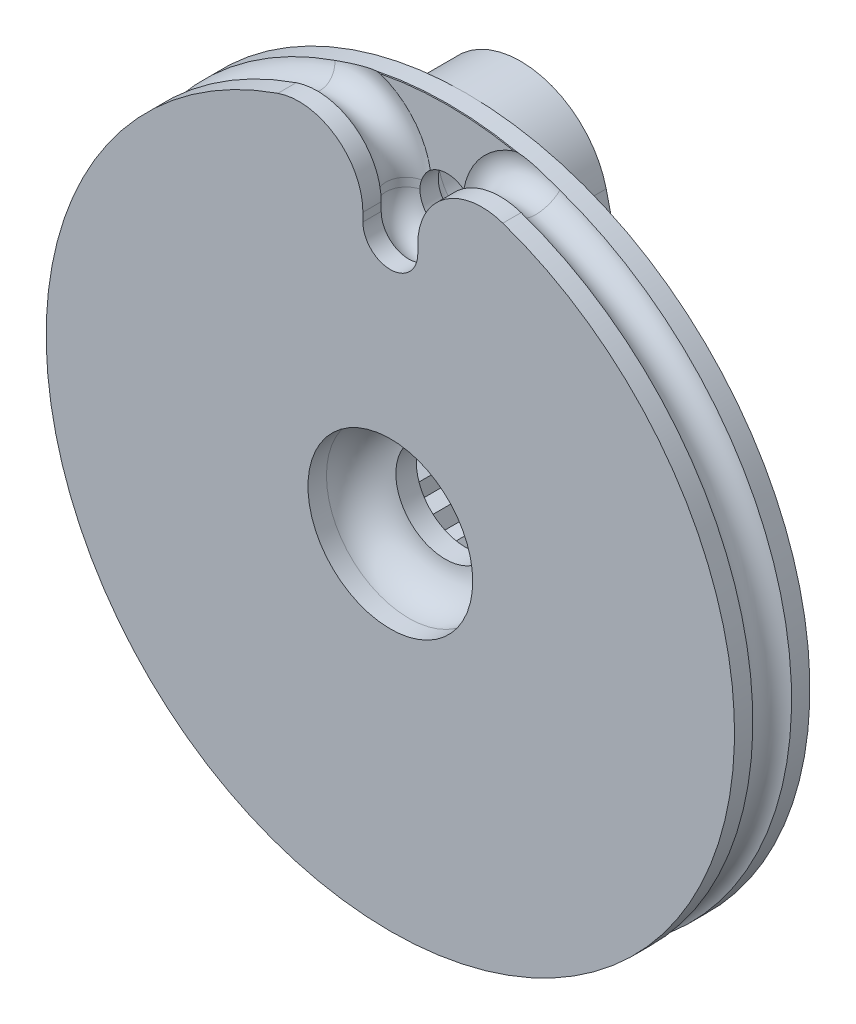
SolidWorks part; units mm, degrees
ref_plane "Front Plane" through (0, 0, 0) normal (0, 0, 1) x (1, 0, 0)
ref_plane "Top Plane" through (0, 0, 0) normal (0, 1, 0) x (1, 0, 0)
ref_plane "Right Plane" through (0, 0, 0) normal (1, 0, 0) x (0, 0, -1)
sketch "Sketch1" plane through (0, 0, 0) normal (0, 1, 0) x (1, 0, 0)
  line L0 (0, 0) -> (0, -4.9195) construction
  line L1 (-4, 1.0292) -> (-9.4, 1.0292)
  line L2 (0, 2.5292) -> (0, -1.0292)
  line L3 (0, -1.0292) -> (-9.4, -1.0292)
  line L5 (-9.4, 1.0292) -> (-9.4, 0.5292)
  line L6 (-9.4, -0.5292) -> (-9.4, -1.0292)
  line L7 (-9, 0.5907) -> (-9, -0.4988) construction
  line L10 (-4, 1.0292) -> (-4, 2.5292)
  line L11 (-4, 2.5292) -> (0, 2.5292)
  arc A0 (-9.4, -0.5292) -> (-9.4, 0.5292) centre (-9.55, 0) ccw
  point P2 (-3.8205, -1.0292)
  point P12 (0, 2.6484)
  point P15 (0, -1.0292)
  point P18 (0, -0.9285)
  point P19 (0, 0)
  point P20 (0, -1.0873)
  dimension "D4" = 0.55
  dimension "D1" = 18
  dimension "D2" = 0.5
  dimension "D3" = 0.5
  dimension "D5" = 0.15
  dimension "D6" = 1.5
  dimension "D7" = 8
revolve "Revolve1" add sketch "Sketch1" angle 360 about L0
sketch "Sketch2" plane through (0, 0, 1.0292) normal (0, 0, -1) x (-1, 0, 0)
  circle A2 centre (0, 0) radius 1.35
  circle A3 centre (0, 7) radius 0.75
  point P0 (0, 0)
  point P9 (0, 0)
  dimension "D3" = 2.7
  dimension "D4" = 1.5
  dimension "D5" = 7
extrude "Cut-Extrude1" cut sketch "Sketch2" along normal up to next
sketch "Sketch3" plane through (0, 0, 1.0292) normal (0, 0, 1) x (1, 0, 0)
  line L0 (0.75, 7) -> (0.75, 7.23)
  line L1 (-0.75, 7) -> (-0.75, 7.23)
  circle A2 centre (0, 7) radius 0.75 construction
  arc A3 (0.75, 7.23) -> (3.0719, 8.8839) centre (2.5, 7.23) cw
  circle A4 centre (0, 0) radius 9.4 construction
  arc A5 (3.0719, 8.8839) -> (-3.0719, 8.8839) centre (0, 0) ccw
  arc A6 (-0.75, 7) -> (0.75, 7) centre (0, 7) ccw
  arc A7 (-0.75, 7.23) -> (-3.0719, 8.8839) centre (-2.5, 7.23) ccw
  point P14 (0, 0)
  point P15 (1.5403, 9.2223)
  dimension "D2" = 1.75
extrude "Cut-Extrude2" cut sketch "Sketch3" against normal blind 0.8
sketch "Sketch5" plane through (0, 0, 1.0292) normal (0, 0, 1) x (1, 0, 0)
  circle A0 centre (0, 0) radius 2.25
  dimension "D1" = 4.5
extrude "Cut-Extrude4" cut sketch "Sketch5" against normal blind 1.5
fillet "Fillet2" radius 1 1 edges at (2.25, 0, -0.4708)
other "Move Face1" flip direction yes face at (0, 7.9097, 0.2292) offset 0.75 parameters "D1"=0.75
sketch "Sketch6" plane through (0, 0, 0) normal (0, 0, 1) x (1, 0, 0)
  line L0 (0.75, 7) -> (0.75, 7.23) construction
  line L1 (0.75, 7) -> (0.75, 7.23)
  line L2 (-0.75, 7.23) -> (-0.75, 7) construction
  line L3 (-0.75, 7.23) -> (-0.75, 7)
  arc A0 (2.7428, 8.963) -> (0.75, 7.23) centre (2.5, 7.23) ccw construction
  arc A1 (3.0719, 8.8839) -> (0.75, 7.23) centre (2.5, 7.23) ccw
  arc A3 (-0.75, 7) -> (0.75, 7) centre (0, 7) ccw
  arc A4 (-0.75, 7) -> (0.75, 7) centre (0, 7) ccw
  arc A6 (-0.75, 7.23) -> (-2.7428, 8.963) centre (-2.5, 7.23) ccw construction
  arc A7 (-0.75, 7.23) -> (-3.0719, 8.8839) centre (-2.5, 7.23) ccw
  point P3 (3.0682, 8.9381)
  point P13 (-3.0682, 8.9381)
sketch "Sketch7" plane through (0, 0, 0) normal (1, 0, 0) x (0, 0, -1)
  line L0 (0, 7) -> (0, 6.25) construction
  circle A0 centre (0, 6.4) radius 0.55
  point P4 (0, 6.25)
  point P5 (0, 0)
  dimension "D1" = 1.1
  dimension "D2" = 0.15
sweep "Cut-Sweep2" cut profiles "Sketch7" path "Sketch6"
sketch "Sketch8" plane through (0, 0, -2.5292) normal (0, 0, -1) x (-1, 0, 0)
  line L0 (-3.8941, 0.9143) -> (-2.3365, 7.5486)
  line L1 (2.3365, 7.5486) -> (3.8941, 0.9143)
  circle A0 centre (0, 0) radius 4 construction
  arc A1 (-2.3365, 7.5486) -> (2.3365, 7.5486) centre (0, 7) cw
  arc A4 (3.8941, 0.9143) -> (-3.8941, 0.9143) centre (0, 0) ccw
  circle A5 centre (0, 0) radius 4 construction
  circle A6 centre (0, 7) radius 1.25
  point P8 (0, 7)
  dimension "D1" = 2.4
  dimension "D2" = 2.5
extrude "Boss-Extrude1" add sketch "Sketch8" against normal up to surface (1.5 mm away) up to face at (-0.75, 7, -1.0292)
sketch "Sketch9" plane through (0, 0, -2.5292) normal (0, 0, -1) x (-1, 0, 0)
  line L0 (0, 0) -> (0, 2.2812)
  line L1 (0, 2.2812) -> (0.3726, 2.4721)
  line L2 (0.3726, 2.4721) -> (0.6724, 2.1799)
  line L3 (0.6724, 2.1799) -> (0, 0)
  circle A0 centre (0, 0) radius 2.5 construction
  circle A1 centre (0, 0) radius 2.2812 construction
  point P7 (0.862, 2.2697)
  dimension "D2" = 5
  dimension "D1" = 17.143
  dimension "D3" = 0.68
extrude "Cut-Extrude5" cut sketch "Sketch9" against normal blind 1.5
pattern_circular "CirPattern1" count 21 over 360 about axis through (0, 0, -2.5302) along (0, 0, 1) of "Cut-Extrude5" reverse direction yes
fillet "Fillet3" radius 0.5 1 edges at (-1.25, 7, -1.0292)
